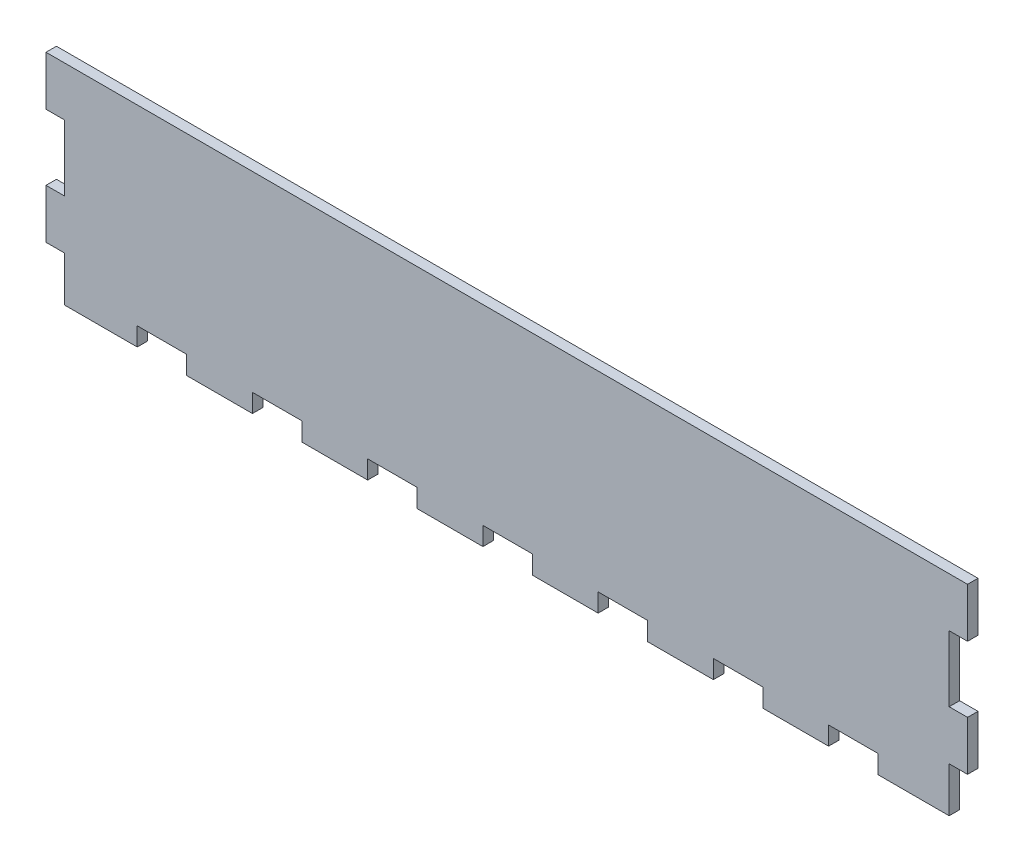
SolidWorks part; units mm, degrees
ref_plane "Front Plane" through (0, 0, 0) normal (0, 0, 1) x (1, 0, 0)
ref_plane "Top Plane" through (0, 0, 0) normal (0, 1, 0) x (1, 0, 0)
ref_plane "Right Plane" through (0, 0, 0) normal (1, 0, 0) x (0, 0, -1)
sketch "Sketch27" plane through (0, 0, 0) normal (0, 0, 1) x (1, 0, 0)
  line L0 (274.7064, -237.6756) -> (274.7064, -252.6756)
  line L1 (274.7064, -202.6756) -> (-5.2016, -202.6756)
  line L2 (274.7064, -202.6756) -> (274.7064, -217.6756)
  line L3 (0.3864, -266.3601) -> (269.1184, -266.3601) construction
  line L4 (-5.2016, -202.6756) -> (-5.2016, -217.6756)
  line L5 (269.1184, -217.6756) -> (274.7064, -217.6756)
  line L6 (269.1184, -217.6756) -> (269.1184, -237.6756)
  line L7 (269.1184, -237.6756) -> (274.7064, -237.6756)
  line L8 (0.3864, -266.3601) -> (22.5064, -266.3601)
  line L9 (274.7064, -252.6756) -> (269.1184, -252.6756)
  line L12 (269.1184, -252.6756) -> (269.1184, -266.3601)
  line L16 (0.3864, -237.6756) -> (-5.2016, -237.6756)
  line L17 (0.3864, -237.6756) -> (0.3864, -217.6756)
  line L18 (0.3864, -217.6756) -> (-5.2016, -217.6756)
  line L19 (0.3864, -252.6756) -> (-5.2016, -252.6756)
  line L20 (0.3864, -252.6756) -> (0.3864, -266.3601)
  line L21 (-5.2016, -237.6756) -> (-5.2016, -252.6756)
  line L22 (134.7524, -202.6756) -> (134.7524, -303.7553) construction
  line L23 (127.5064, -260.7721) -> (142.5064, -260.7721)
  line L24 (127.5064, -260.7721) -> (127.5064, -266.3601)
  line L25 (37.5064, -266.3601) -> (57.5064, -266.3601)
  line L26 (142.5064, -260.7721) -> (142.5064, -266.3601)
  line L27 (72.5064, -266.3601) -> (92.5064, -266.3601)
  line L28 (92.5064, -260.7721) -> (107.5064, -260.7721)
  line L29 (92.5064, -260.7721) -> (92.5064, -266.3601)
  line L30 (107.5064, -260.7721) -> (107.5064, -266.3601)
  line L31 (107.5064, -266.3601) -> (127.5064, -266.3601)
  line L32 (57.5064, -260.7721) -> (72.5064, -260.7721)
  line L33 (57.5064, -260.7721) -> (57.5064, -266.3601)
  line L34 (72.5064, -260.7721) -> (72.5064, -266.3601)
  line L35 (142.5064, -266.3601) -> (162.5064, -266.3601)
  line L36 (22.5064, -260.7721) -> (37.5064, -260.7721)
  line L37 (22.5064, -260.7721) -> (22.5064, -266.3601)
  line L38 (37.5064, -260.7721) -> (37.5064, -266.3601)
  line L39 (177.5064, -266.3601) -> (197.5064, -266.3601)
  line L40 (162.5064, -260.7721) -> (177.5064, -260.7721)
  line L41 (162.5064, -260.7721) -> (162.5064, -266.3601)
  line L42 (177.5064, -260.7721) -> (177.5064, -266.3601)
  line L43 (212.5064, -266.3601) -> (232.5064, -266.3601)
  line L44 (197.5064, -260.7721) -> (212.5064, -260.7721)
  line L45 (197.5064, -260.7721) -> (197.5064, -266.3601)
  line L46 (212.5064, -260.7721) -> (212.5064, -266.3601)
  line L47 (269.1184, -266.3601) -> (247.5064, -266.3601)
  line L48 (232.5064, -260.7721) -> (247.5064, -260.7721)
  line L49 (232.5064, -260.7721) -> (232.5064, -266.3601)
  line L50 (247.5064, -260.7721) -> (247.5064, -266.3601)
  dimension "D1" = 15
  dimension "D2" = 5.588
  dimension "D3" = 5.588
  dimension "D4" = 5.588
  dimension "D5" = 5.588
  dimension "D6" = 5.588
  dimension "D7" = 5.588
extrude "Boss-Extrude1" add sketch "Sketch27" along normal blind 3.175
